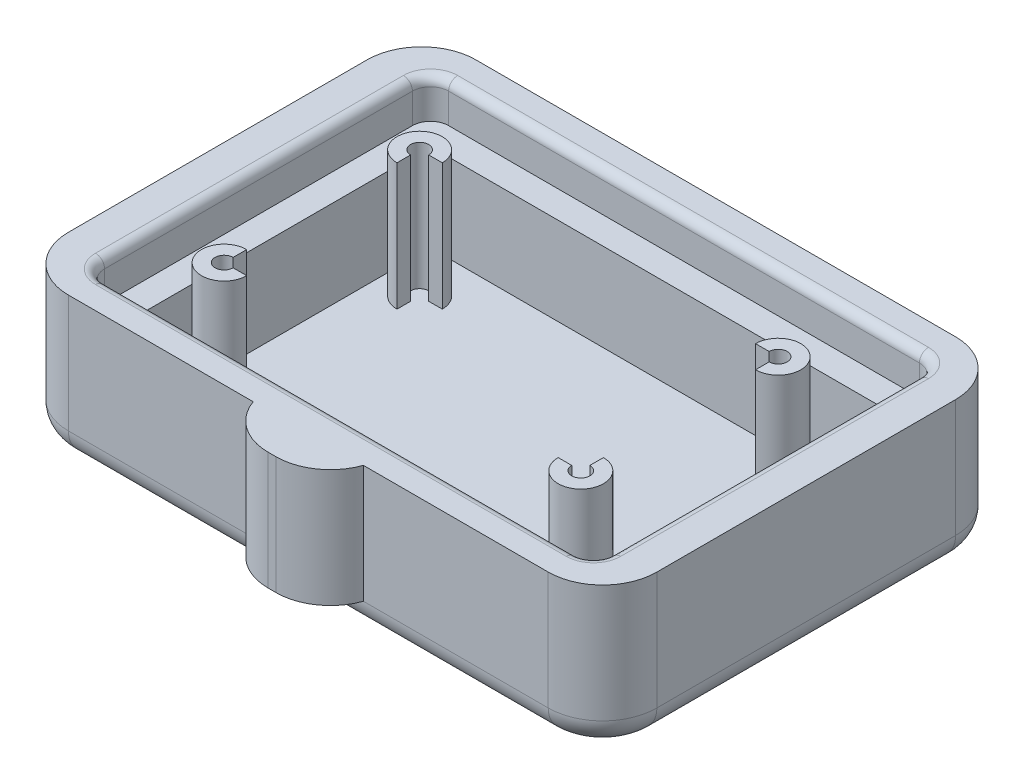
SolidWorks part; units mm, degrees
ref_plane "Front Plane" through (0, 0, 0) normal (0, 0, 1) x (1, 0, 0)
ref_plane "Top Plane" through (0, 0, 0) normal (0, 1, 0) x (1, 0, 0)
ref_plane "Right Plane" through (0, 0, 0) normal (1, 0, 0) x (0, 0, -1)
sketch "Sketch1" plane through (0, 0, 0) normal (0, 1, 0) x (1, 0, 0)
  line L1 (0, 0) -> (82.55, 0)
  line L2 (0, 0) -> (0, 57.15)
  line L3 (0, 57.15) -> (82.55, 57.15)
  line L4 (82.55, 0) -> (82.55, 57.15)
  dimension "D1" = 57.15
  dimension "D2" = 82.55
extrude "Boss-Extrude1" add sketch "Sketch1" along normal blind 20.32
fillet "Fillet2" radius 7.62 4 edges at (82.55, 10.16, -57.15) (82.55, 10.16, 0) (0, 10.16, 0) (0, 10.16, -57.15)
fillet "Fillet3" radius 3.81 8 edges at (80.3182, 0, -54.9182) (82.55, 0, -28.575) (80.3182, 0, -2.2318) (41.275, 0, 0) (2.2318, 0, -2.2318) (0, 0, -28.575) (2.2318, 0, -54.9182) (41.275, 0, -57.15)
sketch "Sketch2" plane through (0, 20.32, 0) normal (0, 1, 0) x (1, 0, 0)
  line L0 (0, 28.575) -> (82.55, 28.575) construction
  line L1 (0, 49.53) -> (0, 7.62) construction
  line L2 (82.55, 7.62) -> (82.55, 49.53) construction
  line L4 (9.525, 8.255) -> (73.025, 8.255)
  line L5 (9.525, 8.255) -> (9.525, 48.895)
  line L6 (9.525, 48.895) -> (73.025, 48.895)
  line L7 (73.025, 8.255) -> (73.025, 48.895)
  line L8 (9.525, 8.255) -> (73.025, 48.895) construction
  line L9 (9.525, 48.895) -> (73.025, 8.255) construction
  point P6 (41.275, 28.575)
  dimension "D1" = 40.64
  dimension "D2" = 63.5
extrude "Cut-Extrude1" cut sketch "Sketch2" against normal blind 17.78
sketch "Sketch7" plane through (0, 20.32, 0) normal (0, 1, 0) x (1, 0, 0)
  line L14 (5.715, 52.705) -> (5.715, 4.445)
  line L15 (5.715, 4.445) -> (76.835, 4.445)
  line L16 (76.835, 4.445) -> (76.835, 52.705)
  line L17 (76.835, 52.705) -> (5.715, 52.705)
  line L18 (5.715, 52.705) -> (5.715, 4.445)
  line L19 (5.715, 4.445) -> (76.835, 4.445)
  line L20 (76.835, 4.445) -> (76.835, 52.705)
  line L21 (76.835, 52.705) -> (5.715, 52.705)
  dimension "D1" = 3.81
sketch "Sketch5" plane through (0, 2.54, 0) normal (0, 1, 0) x (1, 0, 0)
  line L0 (9.525, 48.895) -> (9.525, 8.255) construction
  line L1 (9.525, 8.255) -> (73.025, 8.255) construction
  line L2 (73.025, 48.895) -> (9.525, 48.895) construction
  circle A0 centre (14.605, 42.291) radius 3.175
  circle A1 centre (14.605, 14.859) radius 3.175
  circle A2 centre (64.897, 42.291) radius 3.175
  circle A3 centre (64.8964, 14.605) radius 3.175
  point P16 (0, 0)
  dimension "D5" = 6.35
  dimension "D6" = 6.35
  dimension "D7" = 6.35
  dimension "D8" = 6.35
  dimension "D11" = 6.604
  dimension "D1" = 5.08
  dimension "D2" = 27.432
  dimension "D3" = 27.686
  dimension "D4" = 5.08
  dimension "D9" = 6.604
  dimension "D10" = 50.292
  dimension "D12" = 50.292
sketch "Sketch9" plane through (0, 0, 0) normal (0, 0, 1) x (1, 0, 0)
  line L0 (41.275, 20.32) -> (41.275, 3.81) construction
  line L1 (7.62, 20.32) -> (74.93, 20.32) construction
  line L2 (7.62, 3.81) -> (74.93, 3.81) construction
  line L4 (49.0058, 20.32) -> (33.5442, 20.32)
  line L5 (49.0058, 20.32) -> (49.0058, 3.81)
  line L6 (49.0058, 3.81) -> (33.5442, 3.81)
  line L7 (33.5442, 20.32) -> (33.5442, 3.81)
  line L8 (49.0058, 20.32) -> (33.5442, 3.81) construction
  line L9 (49.0058, 3.81) -> (33.5442, 20.32) construction
  point P6 (41.275, 12.065)
extrude "Boss-Extrude5" add sketch "Sketch9" along normal blind 5.08
fillet "Fillet10" radius 7.62 2 edges at (49.0058, 12.065, 5.08) (33.5442, 12.065, 5.08)
extrude "Cut-Extrude4" cut sketch "Sketch7" against normal blind 5.461
fillet "Fillet12" radius 2.54 4 edges at (76.835, 17.5895, -52.705) (76.835, 17.5895, -4.445) (5.715, 17.5895, -52.705) (5.715, 17.5895, -4.445)
fillet "Fillet13" radius 1.27 8 edges at (6.4589, 20.32, -5.1889) (5.715, 20.32, -28.575) (6.4589, 20.32, -51.9611) (41.275, 20.32, -52.705) (76.0911, 20.32, -51.9611) (76.835, 20.32, -28.575) (76.0911, 20.32, -5.1889) (41.275, 20.32, -4.445)
extrude "Boss-Extrude6" add sketch "Sketch5" along normal blind 17.78
sketch "Sketch11" plane through (0, 20.32, 0) normal (0, 1, 0) x (1, 0, 0)
  circle A0 centre (14.605, 14.859) radius 1.27
  circle A1 centre (14.605, 42.291) radius 1.27
  circle A2 centre (64.8964, 14.605) radius 1.27
  circle A3 centre (64.897, 42.291) radius 1.27
  dimension "D1" = 2.54
  dimension "D2" = 2.54
  dimension "D3" = 2.54
  dimension "D4" = 2.54
extrude "Cut-Extrude5" cut sketch "Sketch11" against normal blind 17.78
sketch "Sketch17" plane through (0, 2.54, 0) normal (0, 1, 0) x (1, 0, 0)
  arc A0 (17.78, 42.291) -> (14.605, 39.116) centre (14.605, 42.291) cw
  circle A2 centre (14.605, 42.291) radius 3.175 construction
  arc A5 (61.7214, 14.605) -> (64.8964, 17.78) centre (64.8964, 14.605) cw
  arc A8 (14.605, 18.034) -> (17.78, 14.859) centre (14.605, 14.859) cw
  circle A9 centre (14.605, 14.859) radius 3.175 construction
  circle A10 centre (64.8964, 14.605) radius 3.175 construction
  arc A11 (63.627, 42.291) -> (64.897, 41.021) centre (64.897, 42.291) ccw
  circle A12 centre (64.897, 42.291) radius 1.27 construction
extrude "Cut-Extrude-Thin1" cut sketch "Sketch17" along normal through all thin
sketch "Sketch18" plane through (0, 20.32, 0) normal (0, 1, 0) x (1, 0, 0)
  line L0 (36.329, -3.6817) -> (46.221, -3.6817) construction
  line L1 (41.275, -5.08) -> (41.9474, 3.175) construction
  line L2 (41.8216, -5.08) -> (40.7284, -5.08) construction
  line L3 (74.295, 3.175) -> (8.255, 3.175) construction
  arc A0 (33.5442, 0) -> (40.7284, -5.08) centre (40.7284, 2.54) ccw construction
  arc A1 (41.8216, -5.08) -> (49.0058, 0) centre (41.8216, 2.54) ccw construction
  circle A2 centre (41.4923, -2.4117) radius 1.1812
  dimension "D1" = 2.54
